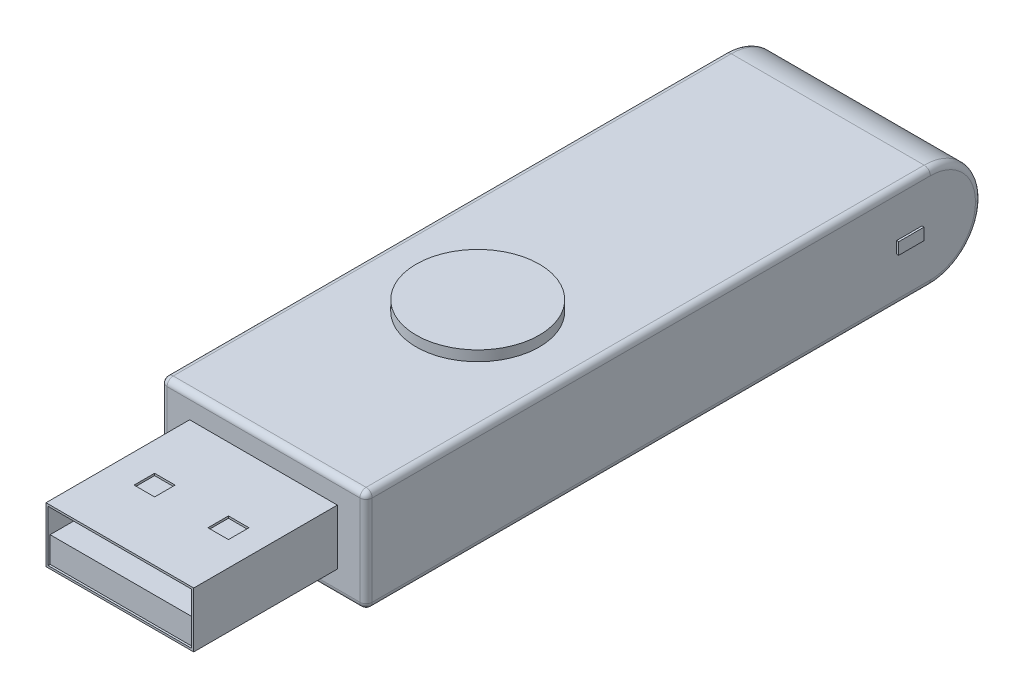
SolidWorks part; units mm, degrees
ref_plane "Front Plane" through (0, 0, 0) normal (0, 0, 1) x (1, 0, 0)
ref_plane "Top Plane" through (0, 0, 0) normal (0, 1, 0) x (1, 0, 0)
ref_plane "Right Plane" through (0, 0, 0) normal (1, 0, 0) x (0, 0, -1)
sketch "Sketch1" plane through (0, 0, 0) normal (0, 0, 1) x (1, 0, 0)
  line L1 (-12.7, 6.35) -> (12.7, 6.35)
  line L2 (-12.7, 6.35) -> (-12.7, -6.35)
  line L3 (-12.7, -6.35) -> (12.7, -6.35)
  line L4 (12.7, 6.35) -> (12.7, -6.35)
  line L5 (-12.7, 6.35) -> (12.7, -6.35) construction
  line L6 (-12.7, -6.35) -> (12.7, 6.35) construction
  point P0 (0, 0)
  dimension "D1" = 25.4
  dimension "D2" = 12.7
extrude "Boss-Extrude1" add sketch "Sketch1" along normal blind 76.2
fillet "Fillet1" radius 6.35 2 edges at (0, 6.35, 0) (0, -6.35, 0)
sketch "Sketch3" plane through (0, 0, 76.2) normal (0, 0, 1) x (1, 0, 0)
  line L0 (-9.144, 3.429) -> (9.144, 3.429)
  line L1 (-8.89, 3.175) -> (8.89, 3.175)
  line L2 (-8.89, 3.175) -> (-8.89, -3.175)
  line L3 (-8.89, -3.175) -> (8.89, -3.175)
  line L4 (8.89, 3.175) -> (8.89, -3.175)
  line L5 (-8.89, 3.175) -> (8.89, -3.175) construction
  line L6 (-8.89, -3.175) -> (8.89, 3.175) construction
  line L7 (9.144, 3.429) -> (9.144, -3.429)
  line L8 (-9.144, -3.429) -> (9.144, -3.429)
  line L9 (-9.144, 3.429) -> (-9.144, -3.429)
  point P0 (0, 0)
  dimension "D1" = 17.78
  dimension "D2" = 6.35
  dimension "D3" = 0.254
extrude "Boss-Extrude2" add sketch "Sketch3" along normal blind 17.78
sketch "Sketch4" plane through (0, 0, 76.2) normal (0, 0, 1) x (1, 0, 0)
  line L0 (-8.89, 0) -> (-8.89, -3.175)
  line L1 (-8.89, 3.175) -> (-8.89, -3.175) construction
  line L2 (-8.89, -3.175) -> (8.89, -3.175)
  line L3 (8.89, -3.175) -> (8.89, 0)
  line L4 (8.89, -3.175) -> (8.89, 3.175) construction
  line L5 (8.89, 0) -> (-8.89, 0)
  point P5 (-8.89, -3.175)
extrude "Boss-Extrude3" add sketch "Sketch4" along normal blind 17.526
sketch "Sketch5" plane through (0, 3.429, 0) normal (0, 1, 0) x (1, 0, 0)
  line L4 (6.1026, -86.6399) -> (3.5626, -86.6399)
  line L5 (-5.5814, -84.0999) -> (-3.0414, -84.0999)
  line L6 (-5.5814, -84.0999) -> (-5.5814, -86.6399)
  line L7 (-5.5814, -86.6399) -> (-3.0414, -86.6399)
  line L8 (-3.0414, -84.0999) -> (-3.0414, -86.6399)
  line L9 (-5.5814, -84.0999) -> (-3.0414, -86.6399) construction
  line L10 (-5.5814, -86.6399) -> (-3.0414, -84.0999) construction
  line L11 (3.5626, -84.0999) -> (3.5626, -86.6399)
  line L12 (6.1026, -84.0999) -> (3.5626, -84.0999)
  line L13 (6.1026, -84.0999) -> (6.1026, -86.6399)
  line L14 (6.1026, -86.6399) -> (3.5626, -84.0999) construction
  line L15 (6.1026, -84.0999) -> (3.5626, -86.6399) construction
  point P9 (-4.3114, -85.3699)
  point P18 (4.572, -85.09)
extrude "Cut-Extrude1" cut sketch "Sketch5" against normal up to vertex (0.254 mm away) up to point (8.89, 3.175, 93.98)
sketch "Sketch7" plane through (0, -3.429, 0) normal (0, -1, 0) x (1, 0, 0)
  line L0 (3.5626, 86.6399) -> (6.1026, 86.6399) construction
  line L1 (6.1026, 86.6399) -> (6.1026, 84.0999) construction
  line L2 (6.1026, 84.0999) -> (3.5626, 84.0999) construction
  line L3 (3.5626, 84.0999) -> (3.5626, 86.6399) construction
  line L12 (-3.0414, 84.0999) -> (-5.5814, 84.0999) construction
  line L13 (-5.5814, 84.0999) -> (-5.5814, 86.6399) construction
  line L14 (-3.0414, 86.6399) -> (-3.0414, 84.0999) construction
  line L15 (-5.5814, 86.6399) -> (-3.0414, 86.6399) construction
  line L16 (3.5626, 86.6399) -> (6.1026, 86.6399)
  line L17 (6.1026, 86.6399) -> (6.1026, 84.0999)
  line L18 (6.1026, 84.0999) -> (3.5626, 84.0999)
  line L19 (3.5626, 84.0999) -> (3.5626, 86.6399)
  line L20 (-3.0414, 84.0999) -> (-5.5814, 84.0999)
  line L21 (-5.5814, 84.0999) -> (-5.5814, 86.6399)
  line L22 (-3.0414, 86.6399) -> (-3.0414, 84.0999)
  line L23 (-5.5814, 86.6399) -> (-3.0414, 86.6399)
  point P1 (0, 0)
  point P6 (9.144, 76.2)
  point P10 (0, 0)
  point P11 (0, 0)
extrude "Cut-Extrude6" cut sketch "Sketch7" against normal blind 0.254
fillet "Fillet2" radius 0.762 8 edges at (-12.7, -6.35, 41.275) (-12.7, -4.4901, 1.8599) (-12.7, 4.4901, 1.8599) (12.7, -6.35, 41.275) (12.7, -4.4901, 1.8599) (12.7, 4.4901, 1.8599) (-12.7, 6.35, 41.275) (12.7, 6.35, 41.275)
fillet "Fillet3" radius 0.762 8 edges at (-12.4768, -6.1268, 76.2) (-12.7, 0, 76.2) (-12.4768, 6.1268, 76.2) (0, 6.35, 76.2) (12.4768, 6.1268, 76.2) (12.7, 0, 76.2) (12.4768, -6.1268, 76.2) (0, -6.35, 76.2)
sketch "Sketch20" plane through (0, 6.35, 0) normal (0, 1, 0) x (1, 0, 0)
  circle A0 centre (0, -49.6768) radius 7.62
  dimension "D1" = 15.24
extrude "Boss-Extrude4" add sketch "Sketch20" along normal blind 1.27
sketch "Sketch21" plane through (0, -6.35, 0) normal (0, -1, 0) x (1, 0, 0)
  circle A0 centre (0, 49.6768) radius 7.62 construction
  circle A1 centre (0, 49.6768) radius 7.62
extrude "Boss-Extrude5" add sketch "Sketch21" along normal blind 1.27
sketch "Sketch23" plane through (12.7, 0, 0) normal (1, 0, 0) x (0, 0, -1)
  line L1 (-10.5232, 0.7282) -> (-7.3865, 0.7282)
  line L2 (-10.5232, 0.7282) -> (-10.5232, -0.7282)
  line L3 (-10.5232, -0.7282) -> (-7.3865, -0.7282)
  line L4 (-7.3865, 0.7282) -> (-7.3865, -0.7282)
  line L5 (-10.5232, 0.7282) -> (-7.3865, -0.7282) construction
  line L6 (-10.5232, -0.7282) -> (-7.3865, 0.7282) construction
  point P0 (-8.9549, 0)
extrude "Boss-Extrude6" add sketch "Sketch23" along normal blind 0.254
